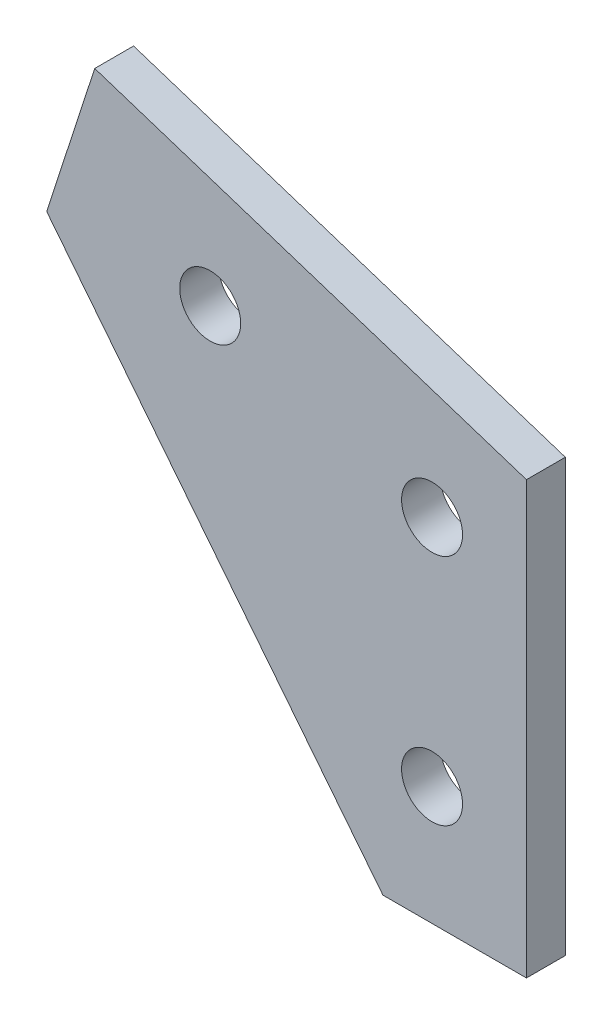
SolidWorks part; units mm, degrees
ref_plane "Front Plane" through (0, 0, 0) normal (0, 0, 1) x (1, 0, 0)
ref_plane "Top Plane" through (0, 0, 0) normal (0, 1, 0) x (1, 0, 0)
ref_plane "Right Plane" through (0, 0, 0) normal (1, 0, 0) x (0, 0, -1)
sketch "Sketch4" plane through (0, 0, 0) normal (0, 0, 1) x (1, 0, 0)
  line L0 (-40.992, 298.8407) -> (-42.9542, 292.8015) construction
  line L1 (-40.992, 298.8407) -> (-53.3542, 260.7936) construction
  line L2 (-42.9542, 292.8015) -> (-7.6984, 281.3461)
  line L3 (-42.9542, 292.8015) -> (-46.8787, 280.723)
  line L4 (-7.6984, 281.3461) -> (-7.6984, 246.1029)
  line L5 (-7.6984, 246.1029) -> (-19.419, 246.1029)
  line L6 (-19.419, 246.1029) -> (-46.8787, 280.723)
extrude "Boss-Extrude1" add sketch "Sketch4" along normal blind 3.175
hole_wizard "#10 Clearance Hole1" positions "Sketch5" profile "Sketch6" hole size "#10" standard "ANSI Inch" end condition through all
sketch "Sketch5" plane through (0, 0, 3.175) normal (0, 0, 1) x (1, 0, 0)
  point P0 (-33.5252, 280.723)
  point P3 (-15.4075, 274.8363)
  point P6 (-15.4075, 255.7863)
sketch "Sketch6" plane through (-33.5252, 280.723, 3.175) normal (1, 0, 0) x (0, -1, 0)
  line L0 (0, 0) -> (0, 3.175)
  line L1 (0, 3.175) -> (2.4892, 3.175)
  line L2 (2.4892, 3.175) -> (2.4892, 0)
  line L5 (2.4892, 0) -> (0, 0)
  line L11 (0, -6.35) -> (0, 107.95) construction
  dimension "Thru Hole Dia." = 4.9784
  dimension "Thru Hole Depth" = 3.175
